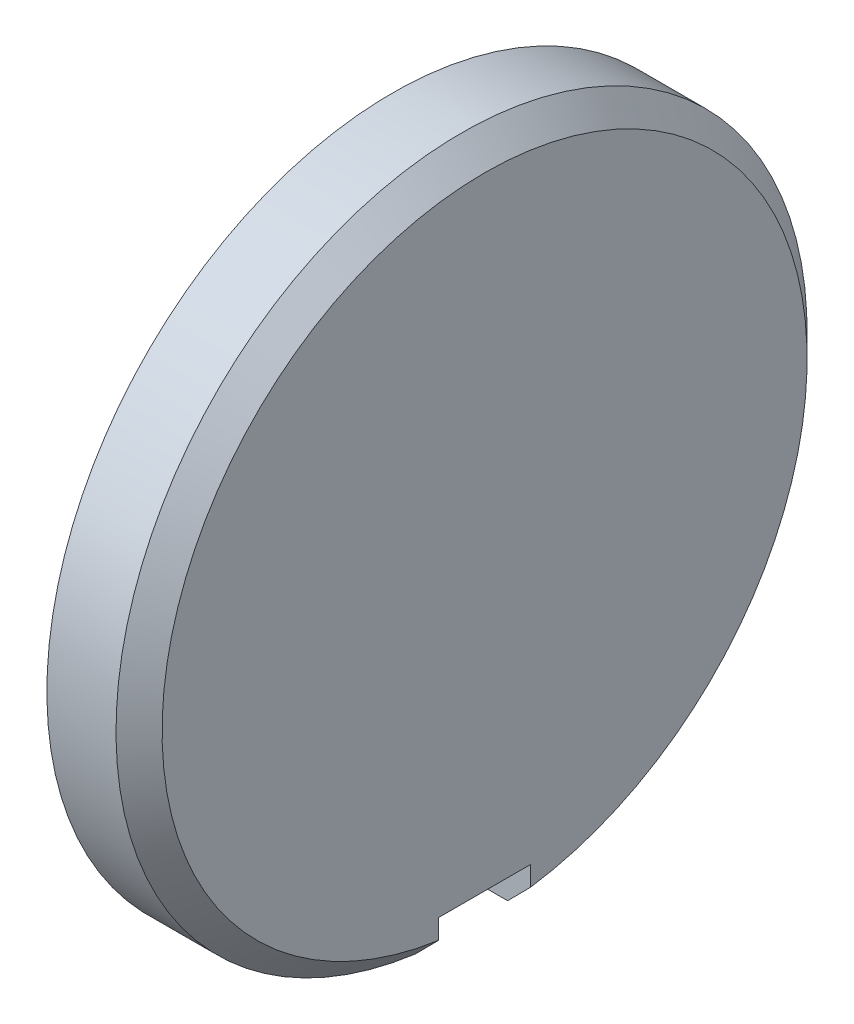
SolidWorks part; units mm, degrees
ref_plane "Front Plane" through (0, 0, 0) normal (0, 0, 1) x (1, 0, 0)
ref_plane "Top Plane" through (0, 0, 0) normal (0, 1, 0) x (1, 0, 0)
ref_plane "Right Plane" through (0, 0, 0) normal (1, 0, 0) x (0, 0, -1)
ref_plane "Plane1" through (0, 0, -52) normal (0, 0, 1) x (1, 0, 0)
sketch "Sketch1" plane through (0, 0, -52) normal (0, 0, 1) x (1, 0, 0)
  line L0 (69, -20) -> (81.8, -20) construction
  line L1 (74, -17.7) -> (75.2, -17.7)
  line L2 (75.2, -17.7) -> (75.2, -20)
  line L3 (75.2, -20) -> (76.8, -20)
  line L4 (76.8, -20) -> (76.8, -14.4)
  line L5 (76.8, -14.4) -> (76.4, -14)
  line L6 (76.4, -14) -> (75.2, -14)
  line L7 (75.2, -14) -> (75.2, -17)
  line L8 (75.2, -17) -> (74, -17)
  line L9 (74, -17) -> (74, -17.7)
revolve "Revolve1" add sketch "Sketch1" angle 360 about L0
sketch "Sketch2" plane through (0, 0, 0) normal (0, 0, 1) x (1, 0, 0)
  line L1 (73.9, -20.4) -> (75.18, -20.4)
  line L2 (73.9, -20.4) -> (73.9, -19.6)
  line L3 (73.9, -19.6) -> (75.18, -19.6)
  line L4 (75.18, -20.4) -> (75.18, -19.6)
extrude "Boss-Extrude1" add sketch "Sketch2" along normal blind 6.4 from offset 55.2 separate body offset against normal yes
combine bodies "Combine1" operation type subtract main body 101 bodies to subtract 102
sketch "Sketch3" plane through (0, 0, 0) normal (0, 0, 1) x (1, 0, 0)
  line L1 (73.9, -23.2) -> (75.18, -23.2)
  line L2 (73.9, -23.2) -> (73.9, -16.8)
  line L3 (73.9, -16.8) -> (75.18, -16.8)
  line L4 (75.18, -23.2) -> (75.18, -16.8)
extrude "Boss-Extrude2" add sketch "Sketch3" along normal blind 0.8 from offset 52.4 separate body offset against normal yes
combine bodies "Combine2" operation type subtract main body 103 bodies to subtract 104
sketch "Sketch4" plane through (0, 0, 0) normal (0, 0, 1) x (1, 0, 0)
  line L1 (75.1, -26.1) -> (76.9, -26.1)
  line L2 (75.1, -26.1) -> (75.1, -25.2)
  line L3 (75.1, -25.2) -> (76.9, -25.2)
  line L4 (76.9, -26.1) -> (76.9, -25.2)
extrude "Boss-Extrude3" add sketch "Sketch4" along normal blind 1.6 from offset 52.8 separate body offset against normal yes
combine bodies "Combine3" operation type subtract main body 105 bodies to subtract 106
